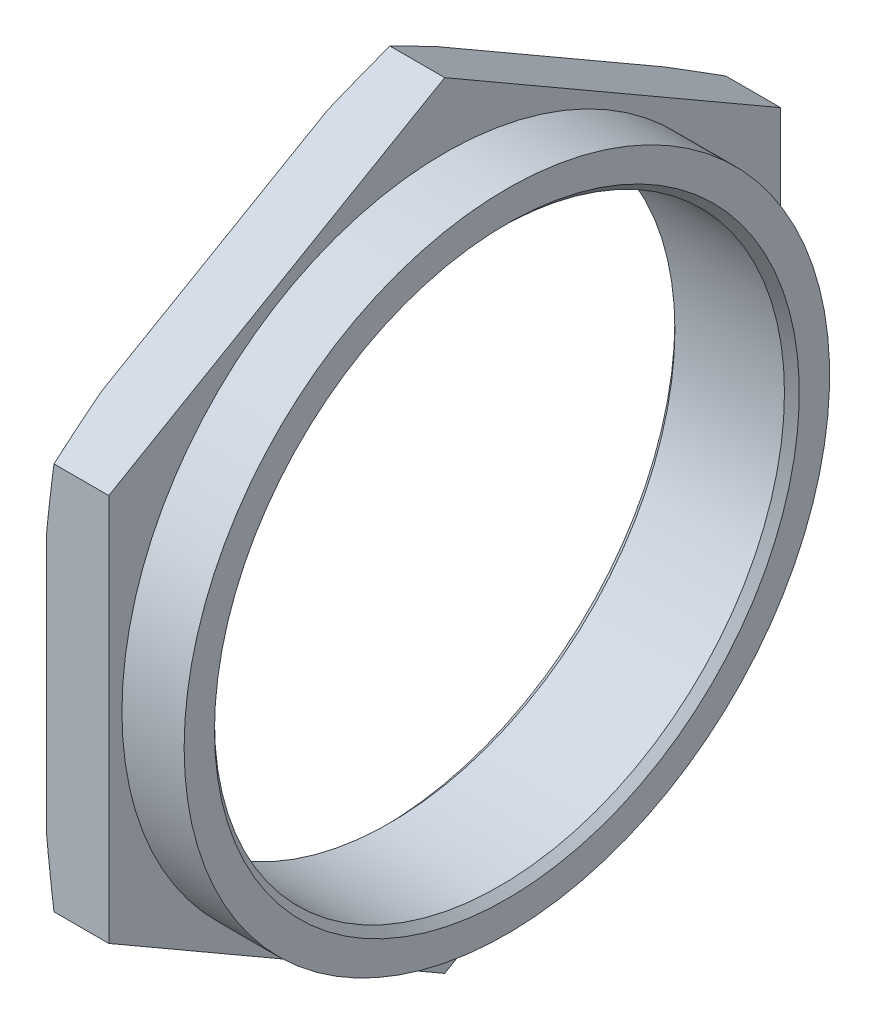
SolidWorks part; units mm, degrees
material "4140"
ref_plane "Front Plane" through (0, 0, 0) normal (0, 0, 1) x (1, 0, 0)
ref_plane "Top Plane" through (0, 0, 0) normal (0, 1, 0) x (1, 0, 0)
ref_plane "Right Plane" through (0, 0, 0) normal (1, 0, 0) x (0, 0, -1)
sketch "Sketch1" plane through (0, 0, 0) normal (0, 0, 1) x (1, 0, 0)
  line L0 (0, 0) -> (77.6492, 0) construction
  line L1 (0, 19.25) -> (0, 26.2)
  line L2 (0, 26.2) -> (4.2, 26.2)
  line L3 (4.2, 26.2) -> (4.2, 21.8)
  line L4 (4.2, 21.8) -> (8.4, 21.8)
  line L5 (8.4, 21.8) -> (8.4, 19.25)
  line L6 (8.4, 19.25) -> (0, 19.25)
  dimension "D1" = 52.4
  dimension "D2" = 43.6
  dimension "D3" = 8.4
  dimension "D4" = 4.2
  dimension "D5" = 38.5
revolve "Revolve1" add sketch "Sketch1" angle 360 about L0
cosmetic thread "Cosmetic Thread1" parameters "D2"=40
chamfer "Chamfer1" distance 0.5 angle 75 1 edges at (0, 0, 26.2) first distance on face at (0, 0, 26.2)
sketch "Sketch2" plane through (0, 0, 0) normal (-1, 0, 0) x (0, 0, 1)
  line L1 (0, 26.2) -> (-22.6899, 13.1)
  line L2 (-22.6899, 13.1) -> (-22.6899, -13.1)
  line L3 (-22.6899, -13.1) -> (0, -26.2)
  line L4 (0, -26.2) -> (22.6899, -13.1)
  line L5 (22.6899, -13.1) -> (22.6899, 13.1)
  line L6 (22.6899, 13.1) -> (0, 26.2)
  circle A0 centre (0, 0) radius 22.6899 construction
  circle A1 centre (0, 0) radius 26.2 construction
  circle A2 centre (0, 0) radius 30.3503
  dimension "D1" = 60.7005
extrude "Extrude1" cut sketch "Sketch2" against normal through all
chamfer "Chamfer2" distance 0.5 angle 45 2 edges at (8.4, 0, 19.25) (0, 0, 19.25)
